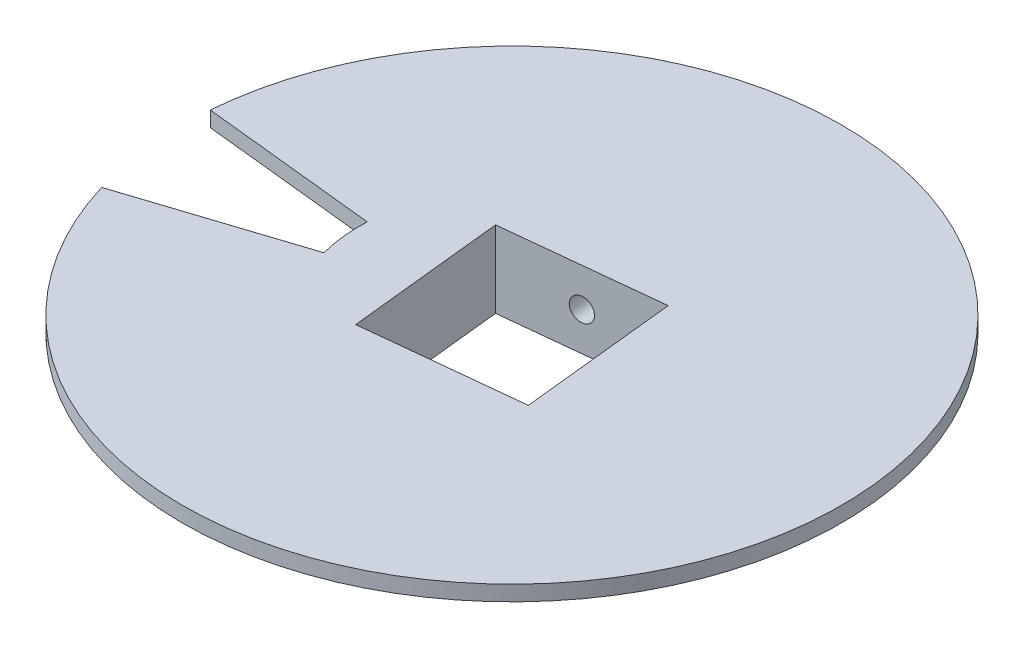
SolidWorks part; units mm, degrees
ref_plane "Front Plane" through (0, 0, 0) normal (0, 0, 1) x (1, 0, 0)
ref_plane "Top Plane" through (0, 0, 0) normal (0, 1, 0) x (1, 0, 0)
ref_plane "Right Plane" through (0, 0, 0) normal (1, 0, 0) x (0, 0, -1)
sketch "Sketch1" plane through (0, 0, 0) normal (0, 1, 0) x (1, 0, 0)
  line L0 (-1.8271, 0.8135) -> (1.8271, -0.8135)
  line L1 (-2, 0) -> (2, 0)
  line L2 (-2, 0) -> (-2, -89.9778)
  line L3 (-2, -89.9778) -> (2, -89.9778)
  line L4 (2, 0) -> (2, -89.9778)
  line L5 (-1.8271, 0.8135) -> (-38.4243, -81.3853)
  line L6 (-38.4243, -81.3853) -> (-34.7702, -83.0123)
  line L7 (1.8271, -0.8135) -> (-34.7702, -83.0123)
  line L8 (-1.3383, 1.4863) -> (1.3383, -1.4863)
  line L9 (-1.3383, 1.4863) -> (-68.2048, -58.7206)
  line L10 (-68.2048, -58.7206) -> (-65.5283, -61.6932)
  line L11 (1.3383, -1.4863) -> (-65.5283, -61.6932)
  line L12 (-0.618, 1.9021) -> (0.618, -1.9021)
  line L13 (-0.618, 1.9021) -> (-86.192, -25.9025)
  line L14 (-86.192, -25.9025) -> (-84.9559, -29.7068)
  line L15 (0.618, -1.9021) -> (-84.9559, -29.7068)
  line L16 (0.2091, 1.989) -> (-0.2091, -1.989)
  line L17 (0.2091, 1.989) -> (-89.2758, 11.3943)
  line L18 (-89.2758, 11.3943) -> (-89.6939, 7.4162)
  line L19 (-0.2091, -1.989) -> (-89.6939, 7.4162)
  line L20 (1, 1.7321) -> (-1, -1.7321)
  line L21 (1, 1.7321) -> (-76.923, 46.7209)
  line L22 (-76.923, 46.7209) -> (-78.923, 43.2568)
  line L23 (-1, -1.7321) -> (-78.923, 43.2568)
  line L24 (1.618, 1.1756) -> (-1.618, -1.1756)
  line L25 (1.618, 1.1756) -> (-51.2696, 73.9691)
  line L26 (-51.2696, 73.9691) -> (-54.5056, 71.618)
  line L27 (-1.618, -1.1756) -> (-54.5056, 71.618)
  line L28 (1.9563, 0.4158) -> (-1.9563, -0.4158)
  line L29 (1.9563, 0.4158) -> (-16.7511, 88.4274)
  line L30 (-16.7511, 88.4274) -> (-20.6637, 87.5957)
  line L31 (-1.9563, -0.4158) -> (-20.6637, 87.5957)
  line L32 (1.9563, -0.4158) -> (-1.9563, 0.4158)
  line L33 (1.9563, -0.4158) -> (20.6637, 87.5957)
  line L34 (20.6637, 87.5957) -> (16.7511, 88.4274)
  line L35 (-1.9563, 0.4158) -> (16.7511, 88.4274)
  line L36 (1.618, -1.1756) -> (-1.618, 1.1756)
  line L37 (1.618, -1.1756) -> (54.5056, 71.618)
  line L38 (54.5056, 71.618) -> (51.2696, 73.9691)
  line L39 (-1.618, 1.1756) -> (51.2696, 73.9691)
  line L40 (1, -1.7321) -> (-1, 1.7321)
  line L41 (1, -1.7321) -> (78.923, 43.2568)
  line L42 (78.923, 43.2568) -> (76.923, 46.7209)
  line L43 (-1, 1.7321) -> (76.923, 46.7209)
  line L44 (0.2091, -1.989) -> (-0.2091, 1.989)
  line L45 (0.2091, -1.989) -> (89.6939, 7.4162)
  line L46 (89.6939, 7.4162) -> (89.2758, 11.3943)
  line L47 (-0.2091, 1.989) -> (89.2758, 11.3943)
  line L48 (-0.618, -1.9021) -> (0.618, 1.9021)
  line L49 (-0.618, -1.9021) -> (84.9559, -29.7068)
  line L50 (84.9559, -29.7068) -> (86.192, -25.9025)
  line L51 (0.618, 1.9021) -> (86.192, -25.9025)
  line L52 (-1.3383, -1.4863) -> (1.3383, 1.4863)
  line L53 (-1.3383, -1.4863) -> (65.5283, -61.6932)
  line L54 (65.5283, -61.6932) -> (68.2048, -58.7206)
  line L55 (1.3383, 1.4863) -> (68.2048, -58.7206)
  line L56 (-1.8271, -0.8135) -> (1.8271, 0.8135)
  line L57 (-1.8271, -0.8135) -> (34.7702, -83.0123)
  line L58 (34.7702, -83.0123) -> (38.4243, -81.3853)
  line L59 (1.8271, 0.8135) -> (38.4243, -81.3853)
  circle A1 centre (0, 0) radius 90
  point P7 (0, 0)
  point P126 (0, 0)
  dimension "D1" = 180
  dimension "D2" = 4
  dimension "D3" = 15
sketch "Sketch7" plane through (0, 0, 0) normal (0, 0, 1) x (1, 0, 0)
  line L6 (0, 0) -> (-86, 0)
  line L7 (0, 0) -> (0, -4)
  line L8 (0, -4) -> (-86, -4)
  line L9 (-86, 0) -> (-86, -4)
  dimension "D1" = 4
  dimension "D2" = 86
revolve "Revolve4" add sketch "Sketch7" angle 360 about L7
sketch "Sketch9" plane through (0, 0, 0) normal (0, 1, 0) x (1, 0, 0)
  circle A0 centre (0, 0) radius 40
  dimension "D1" = 80
extrude "Cut-Extrude3" cut sketch "Sketch9" against normal through all and the other way through all
extrude "Cut-Extrude4" cut sketch "Sketch1" against normal through all contours L19 A1 L13 region at (-62.5121, 0, 6.5703)
ref_plane "Plane1" through (0, 0, 0) normal (0, -1, 0) x (-1, 0, 0)
sketch "Sketch10" plane through (0, 0, 0) normal (0, -1, 0) x (-1, 0, 0)
  circle A0 centre (0, 0) radius 40
extrude "Boss-Extrude1" add sketch "Sketch10" along normal blind 20
sketch "Sketch14" plane through (0, 0, 0) normal (0, 1, 0) x (1, 0, 0)
  line L0 (-39.7809, -4.1811) -> (0, 0) construction
  line L1 (18.2449, 22.5305) -> (-22.5305, 18.2449)
  line L2 (-22.5305, 18.2449) -> (-18.2449, -22.5305)
  line L3 (-18.2449, -22.5305) -> (22.5305, -18.2449)
  line L4 (22.5305, -18.2449) -> (18.2449, 22.5305)
  arc A1 (-39.9402, 2.1869) -> (-38.6127, -10.4431) centre (0, 0) ccw construction
  arc A10 (-39.9402, 2.1869) -> (-38.6127, -10.4431) centre (0, 0) ccw construction
  dimension "D3" = 20.5
  dimension "D1" = 41
  dimension "D2" = 20.5
extrude "Cut-Extrude7" cut sketch "Sketch14" against normal through all contours L3 L4 L1 L2 region at (0, 0, 0)
sketch "Sketch15" plane through (-2.1428, 0, -20.3877) normal (0.1045, 0, 0.9945) x (0.9945, 0, -0.1045)
  line L0 (20.5, 0) -> (-20.5, 0) construction
  line L2 (20.5, -20) -> (20.5, 0) construction
  circle A0 centre (0, -10) radius 3
  dimension "D1" = 6
  dimension "D2" = 10
  dimension "D4" = 20.5
extrude "Cut-Extrude8" cut sketch "Sketch15" against normal through all and the other way through all
